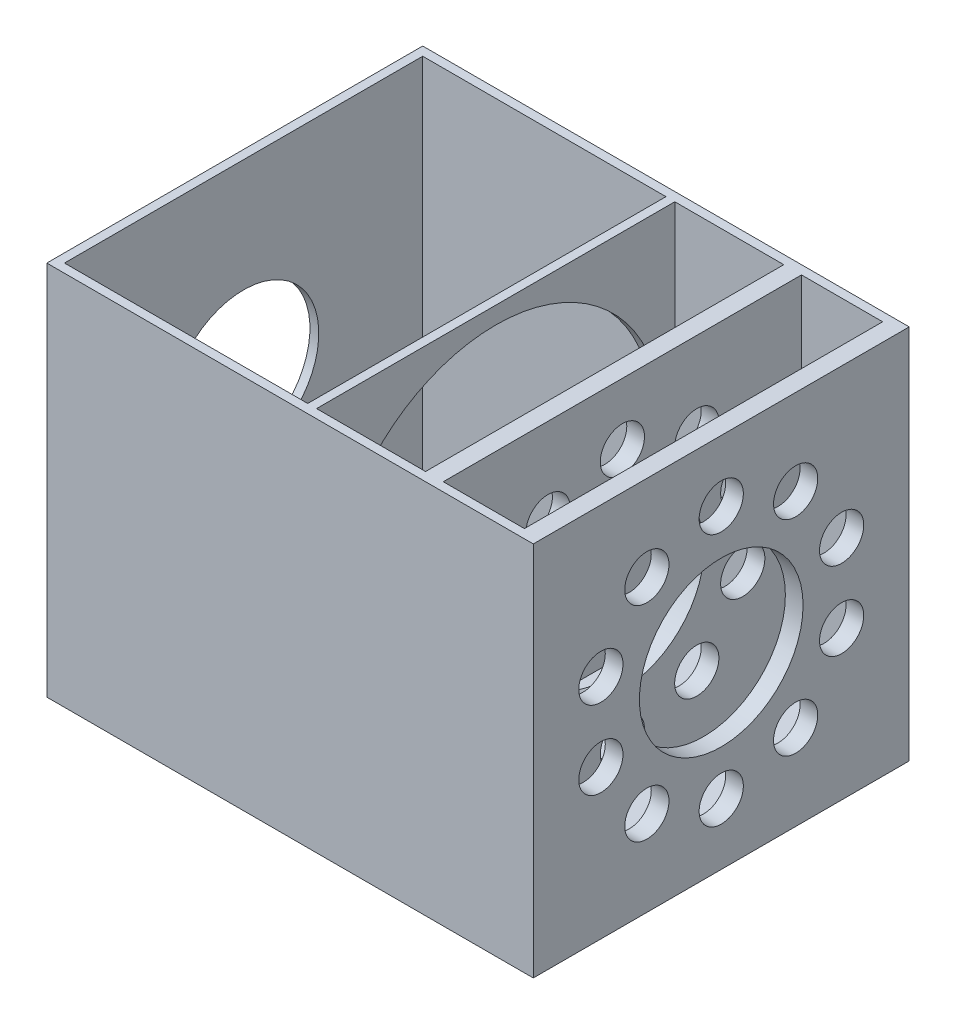
SolidWorks part; units mm, degrees
ref_plane "Front Plane" through (0, 0, 0) normal (0, 0, 1) x (1, 0, 0)
ref_plane "Top Plane" through (0, 0, 0) normal (0, 1, 0) x (1, 0, 0)
ref_plane "Right Plane" through (0, 0, 0) normal (1, 0, 0) x (0, 0, -1)
sketch "Sketch1" plane through (0, 0, 0) normal (0, 1, 0) x (1, 0, 0)
  line L1 (0, 0) -> (110, 0)
  line L2 (0, 0) -> (0, 85)
  line L3 (0, 85) -> (110, 85)
  line L4 (110, 0) -> (110, 85)
  line L5 (55, 85) -> (55, 0) construction
  line L6 (0, 42.5) -> (110, 42.5) construction
  point P188 (55, 42.5)
  dimension "D1" = 85
  dimension "D2" = 110
extrude "Boss-Extrude1" add sketch "Sketch1" along normal blind 85 contours L3 L4 L1 L2
sketch "Sketch2" plane through (0, 0, 0) normal (-1, 0, 0) x (0, 0, 1)
  line L0 (-85, 0) -> (0, 85) construction
  line L1 (0, 85) -> (0, 0) construction
  circle A0 centre (-42.5, 42.5) radius 17
  dimension "D1" = 34
sketch "Sketch3" plane through (110, 0, 0) normal (1, 0, 0) x (0, 0, -1)
  circle A0 centre (42.5, 42.5) radius 18.5
  circle A1 centre (42.5, 71.1194) radius 5
  circle A2 centre (59.322, 65.6536) radius 5
  circle A3 centre (69.7186, 51.3439) radius 5
  circle A4 centre (69.7186, 33.6561) radius 5
  circle A5 centre (59.322, 19.3464) radius 5
  circle A6 centre (42.5, 13.8806) radius 5
  circle A7 centre (25.678, 19.3464) radius 5
  circle A8 centre (15.2814, 33.6561) radius 5
  circle A9 centre (15.2814, 51.3439) radius 5
  circle A10 centre (25.678, 65.6536) radius 5
  dimension "D1" = 37
  dimension "D2" = 10
  dimension "D3" = 10
sketch "Sketch4" plane through (0, 85, 0) normal (0, 1, 0) x (1, 0, 0)
  line L4 (57, 83) -> (57, 2)
  line L5 (59, 83) -> (59, 2)
  line L6 (2, 2) -> (57, 2)
  line L7 (59, 2) -> (83.6441, 2)
  line L8 (2, 83) -> (2, 2)
  line L9 (2, 2) -> (108, 2)
  line L10 (108, 2) -> (108, 83)
  line L11 (108, 83) -> (2, 83)
  line L12 (2, 83) -> (2, 2)
  line L14 (106, 2) -> (106, 83)
  line L16 (59, 83) -> (83.6441, 83)
  line L17 (2, 83) -> (57, 83)
  line L19 (83.6441, 83) -> (83.6441, 2)
  line L20 (87.6441, 83) -> (87.6441, 2)
  line L21 (87.6441, 2) -> (106, 2)
  line L22 (87.6441, 83) -> (106, 83)
  line L24 (110, 0) -> (110, 85) construction
  dimension "D2" = 2
  dimension "D3" = 4
  dimension "D4" = 4
  dimension "D5" = 55
  dimension "D1" = 2
extrude "Cut-Extrude1" cut sketch "Sketch4" against normal blind 83
extrude "Cut-Extrude2" cut sketch "Sketch3" against normal blind 30 contours A0
extrude "Cut-Extrude3" cut sketch "Sketch2" against normal blind 2 contours A0
sketch "Sketch6" plane through (57, 0, 0) normal (-1, 0, 0) x (0, 0, 1)
  line L0 (-2, 85) -> (-83, 2) construction
  circle A0 centre (-42.5131, 43.6194) radius 37.5
  dimension "D1" = 75
extrude "Cut-Extrude4" cut sketch "Sketch6" against normal blind 2 contours A0
extrude "Cut-Extrude5" cut sketch "Sketch3<3>" against normal blind 40
sketch "Sketch3<3>" plane through (110, 0, 0) normal (1, 0, 0) x (0, 0, -1) same geometry as "Sketch3"
